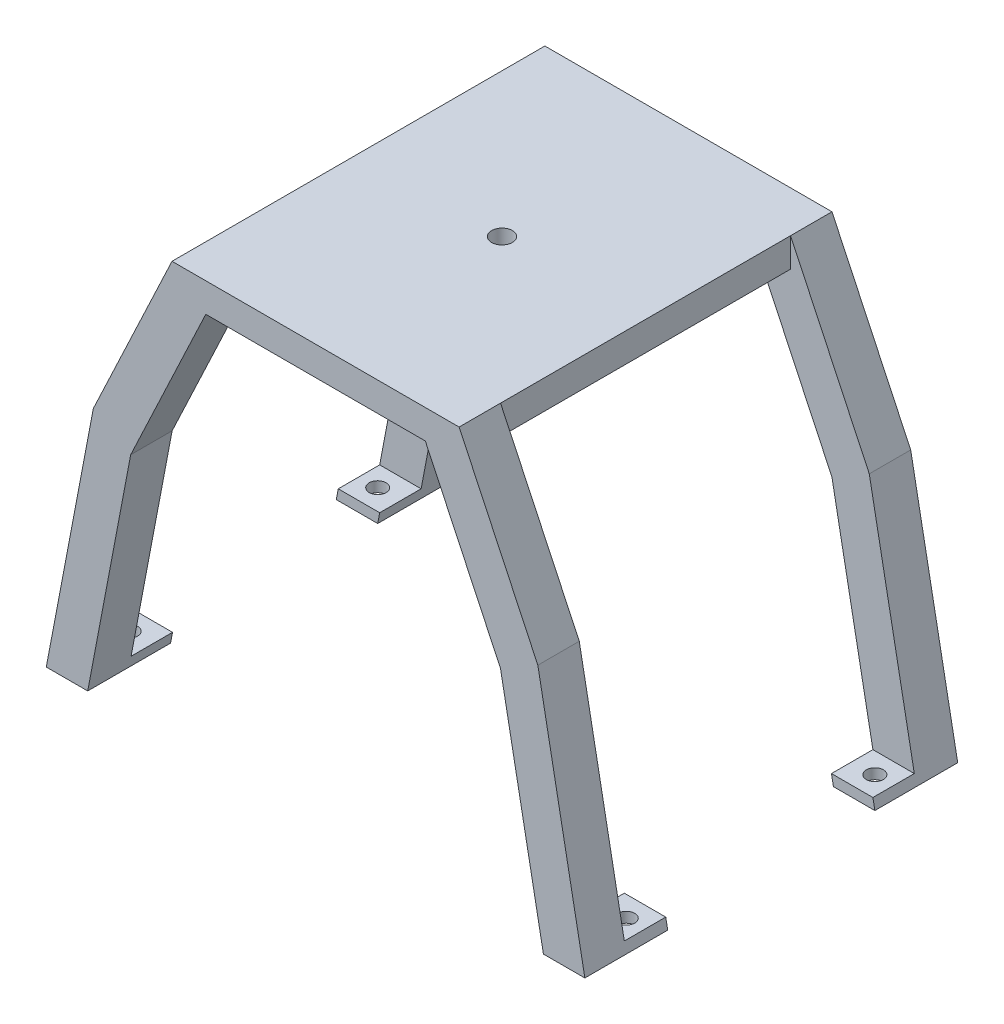
SolidWorks part; units mm, degrees
ref_plane "Front Plane" through (0, 0, 0) normal (0, 0, 1) x (1, 0, 0)
ref_plane "Top Plane" through (0, 0, 0) normal (0, 1, 0) x (1, 0, 0)
ref_plane "Right Plane" through (0, 0, 0) normal (1, 0, 0) x (0, 0, -1)
sketch "Sketch1" plane through (0, 0, 0) normal (0, 0, 1) x (1, 0, 0)
  line L0 (0, 0) -> (11.3493, 59.7188)
  line L1 (11.3493, 59.7188) -> (30.3497, 100)
  line L5 (0, 0) -> (10, 0)
  line L6 (10, 0) -> (20.3683, 54.5568)
  line L7 (20.3683, 54.5568) -> (38.5017, 93)
  line L11 (120, 0) -> (130, 0)
  line L12 (5, 0) -> (125, 0)
  line L13 (65, 0) -> (65, 29.588)
  line L14 (65, 93) -> (65, 100)
  line L15 (99.6503, 100) -> (30.3497, 100)
  line L16 (91.4983, 93) -> (38.5017, 93)
  line L17 (109.6317, 54.5568) -> (91.4983, 93)
  line L18 (120, 0) -> (109.6317, 54.5568)
  line L19 (118.6507, 59.7188) -> (99.6503, 100)
  line L20 (130, 0) -> (118.6507, 59.7188)
  point P11 (5, 0)
  point P14 (125, 0)
  dimension "D1" = 100
  dimension "D2" = 120
  dimension "D3" = 7
  dimension "D4" = 10
extrude "Boss-Extrude1" add sketch "Sketch1" along normal blind 10 contours L15 L1 L0 L5 L6 L7 L16 L17 L18 L11 L20 L19
pattern_linear "LPattern1" count 2 spacing 80 along (0, 0, -1) of "Boss-Extrude1"
sketch "Sketch2" plane through (0, 100, 0) normal (0, 1, 0) x (1, 0, 0)
  line L1 (30.3497, 80) -> (99.6503, 80)
  line L2 (30.3497, 80) -> (30.3497, -10)
  line L3 (30.3497, -10) -> (99.6503, -10)
  line L4 (99.6503, 80) -> (99.6503, -10)
extrude "Boss-Extrude2" add sketch "Sketch2" against normal up to surface (7 mm away) up to face at (65, 93, 5)
sketch "Sketch3" plane through (0, 93, 0) normal (0, -1, 0) x (1, 0, 0)
  line L1 (91.4983, 10) -> (38.5017, 10) construction
  line L2 (30.3497, -70) -> (30.3497, 0) construction
  circle A0 centre (65, -35) radius 2.5
  point P5 (65, 10)
  point P9 (30.3497, -35)
  dimension "D1" = 5
extrude "Cut-Extrude1" cut sketch "Sketch3" against normal blind 10
sketch "Sketch4" plane through (0, 0, -70) normal (0, 0, 1) x (1, 0, 0)
  line L0 (0, 0) -> (10, 0)
  line L1 (0, 0) -> (10, 0) construction
  line L2 (10, 0) -> (10.4751, 2.5)
  line L3 (10, 0) -> (20.3683, 54.5568) construction
  line L4 (10.4751, 2.5) -> (0.4751, 2.5)
  line L5 (0, 0) -> (11.3493, 59.7188) construction
  line L6 (0.4751, 2.5) -> (0, 0)
  line L7 (65, 93) -> (65, 70.5985)
  line L8 (91.4983, 93) -> (38.5017, 93) construction
  line L9 (129.5249, 2.5) -> (130, 0)
  line L10 (130, 0) -> (120, 0)
  line L11 (120, 0) -> (119.5249, 2.5)
  line L12 (119.5249, 2.5) -> (129.5249, 2.5)
  line M9 (109.6317, 54.5568) -> (120, 0)
  line M10 (120, 0) -> (130, 0)
  line M11 (130, 0) -> (118.6507, 59.7188)
  dimension "D1" = 2.5
extrude "Boss-Extrude3" add sketch "Sketch4" along normal blind 77 contours L12 M9 M10 M11 | L0 L2 L4 L6 region at (124.7624, 1.25, -70)
sketch "Sketch5" plane through (0, 2.5, 0) normal (0, 1, 0) x (1, 0, 0)
  line L0 (129.5249, 70) -> (118.6507, 70) construction
  line L5 (119.5249, 0) -> (119.5249, 70) construction
  line L6 (119.5249, 60) -> (139.9226, 60)
  line L7 (119.5249, 60) -> (119.5249, 10)
  line L8 (119.5249, 10) -> (139.9226, 10)
  line L9 (139.9226, 60) -> (139.9226, 10)
  line L11 (129.5249, 0) -> (118.6507, 0) construction
  line L12 (129.5249, 0) -> (119.5249, 0) construction
  line L13 (119.5249, 10) -> (129.5249, 10)
  line L14 (129.5249, 0) -> (129.5249, 70) construction
  line L16 (65, -10) -> (65, 35)
  line L17 (99.6503, -10) -> (30.3497, -10) construction
  line L18 (10.4751, 10) -> (-9.9226, 10)
  line L19 (-9.9226, 60) -> (-9.9226, 10)
  line L20 (10.4751, 60) -> (-9.9226, 60)
  line L21 (10.4751, 60) -> (10.4751, 10)
  line L22 (130, -10) -> (130, 80) construction
  circle A0 centre (125, 65) radius 2.05
  circle A1 centre (125, 5) radius 2.05
  circle A2 centre (5, 5) radius 2.05
  circle A3 centre (5, 65) radius 2.05
  point P10 (124.0878, 70)
  line M9 (129.5249, 0) -> (129.5249, 70)
  dimension "D5" = 4.1
  dimension "D1" = 10
  dimension "D2" = 10
  dimension "D3" = 60
  dimension "D4" = 5
  dimension "D6" = 5
  dimension "D7" = 120
extrude "Cut-Extrude2" cut sketch "Sketch5" against normal blind 10 contours A1 | A2 | L21 L20 L19 L18 | L9 L6 L8 M9 | A0 | A3 | L7 L6 L9 L8 region at (134.7238, 2.5, -35) region at (0.2762, 2.5, -35) region at (125, 2.5, -5) region at (5, 2.5, -5)
